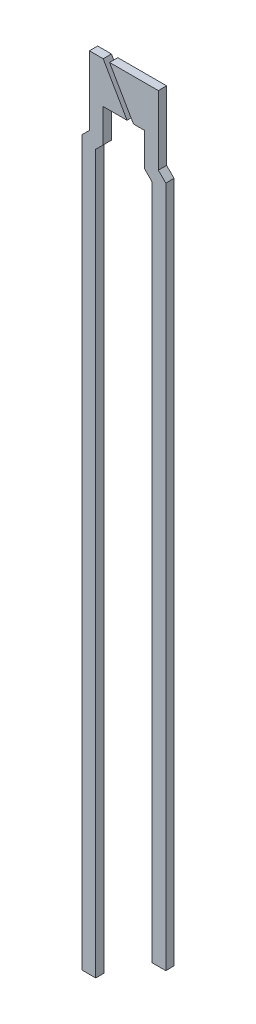
SolidWorks part; units mm, degrees
material "Nickel"
ref_plane "Front Plane" through (0, 0, 0) normal (0, 0, 1) x (1, 0, 0)
ref_plane "Top Plane" through (0, 0, 0) normal (0, 1, 0) x (1, 0, 0)
ref_plane "Right Plane" through (0, 0, 0) normal (1, 0, 0) x (0, 0, -1)
sketch "Sketch1" plane through (0, 0, 0) normal (0, 0, 1) x (1, 0, 0)
  line L0 (0, -507.9946) -> (0, 24891.7341) construction
  line L1 (-1.27, -27) -> (-1.27, -4.6736) construction
  line L2 (1.27, -25.5) -> (1.27, -4.6736) construction
  line L3 (1.02, -0.9771) -> (1.02, -25.5)
  line L4 (1.02, -25.5) -> (1.52, -25.5)
  line L5 (1.52, -0.77) -> (1.52, -25.5)
  line L6 (-1.52, -0.77) -> (-1.25, -0.5)
  line L7 (-1.02, -0.9771) -> (-1.02, -27)
  line L8 (-1.02, -27) -> (-1.52, -27)
  line L9 (-1.52, -0.77) -> (-1.52, -27)
  line L10 (-1.02, -0.9771) -> (-0.75, -0.7071)
  line L11 (-0.75, -0.7071) -> (-0.75, 0.5)
  line L12 (-1.25, -0.5) -> (-1.25, 0.5)
  line L13 (1.25, -0.5) -> (1.25, 0.5)
  line L14 (0.75, -0.7071) -> (0.75, 0.5)
  line L15 (1.02, -0.9771) -> (0.75, -0.7071)
  line L16 (1.52, -0.77) -> (1.25, -0.5)
  line L17 (-0.75, 0.5) -> (0.116, 0.5)
  line L18 (0.116, 0.5) -> (-0.75, 2)
  line L19 (-0.75, 2) -> (-1.25, 2)
  line L20 (-1.25, 2) -> (-1.25, 0.5)
  line L21 (-0.5191, 2) -> (1.25, 2)
  line L22 (1.25, 2) -> (1.25, 0.5)
  line L23 (0.75, 0.5) -> (0.347, 0.5)
  line L24 (0.347, 0.5) -> (-0.5191, 2)
  dimension "D1" = 0.5
  dimension "Pitch" = 2.54
  dimension "D2" = 0.5
  dimension "D3" = 1.5
  dimension "D4" = 2.5
  dimension "D5" = 1.5
  dimension "D6" = 0.5
  dimension "D7" = 60
  dimension "D8" = 0.2
  dimension "D9" = 45
  dimension "D10" = 27
  dimension "D11" = 0.5
  dimension "pin offset" = 1
extrude "Boss-Extrude1" add sketch "Sketch1" along normal mid plane 0.3
sketch "Sketch2" plane through (0, 0, 0.15) normal (0, 0, 1) x (1, 0, 0)
  line L0 (-1.52, -5) -> (1.52, -5)
  line L1 (-1.52, -0.77) -> (-1.52, -27) construction
  line L2 (1.52, -25.5) -> (1.52, -0.77) construction
  dimension "D1" = 5
extrude "Cut-Extrude1" [suppressed] cut sketch "Sketch2" against normal through all and the other way through all flip side to cut
sketch "Sketch4" plane through (0, 0, 0) normal (0, 0, 1) x (1, 0, 0)
  line L0 (-1.27, -5.7303) -> (-1.27, -0.9771) construction
  line L2 (1.27, -5.7303) -> (1.27, -0.9771) construction
  line L4 (-1.52, -0.9771) -> (-1.02, -0.9771) construction
  line L5 (1.02, -0.9771) -> (1.52, -0.9771) construction
  line L6 (1.52, -25.5) -> (1.52, -0.77) construction
  line L7 (1.02, -0.9771) -> (1.02, -25.5) construction
  line L8 (-1.02, -27) -> (-1.02, -0.9771) construction
  line L9 (-1.52, -0.77) -> (-1.52, -27) construction
ref_axis "Anode" through (-1.27, -5.7303, 0) along (0, 1, 0)
ref_axis "Cathode" through (1.27, -5.7303, 0) along (0, 1, 0)
